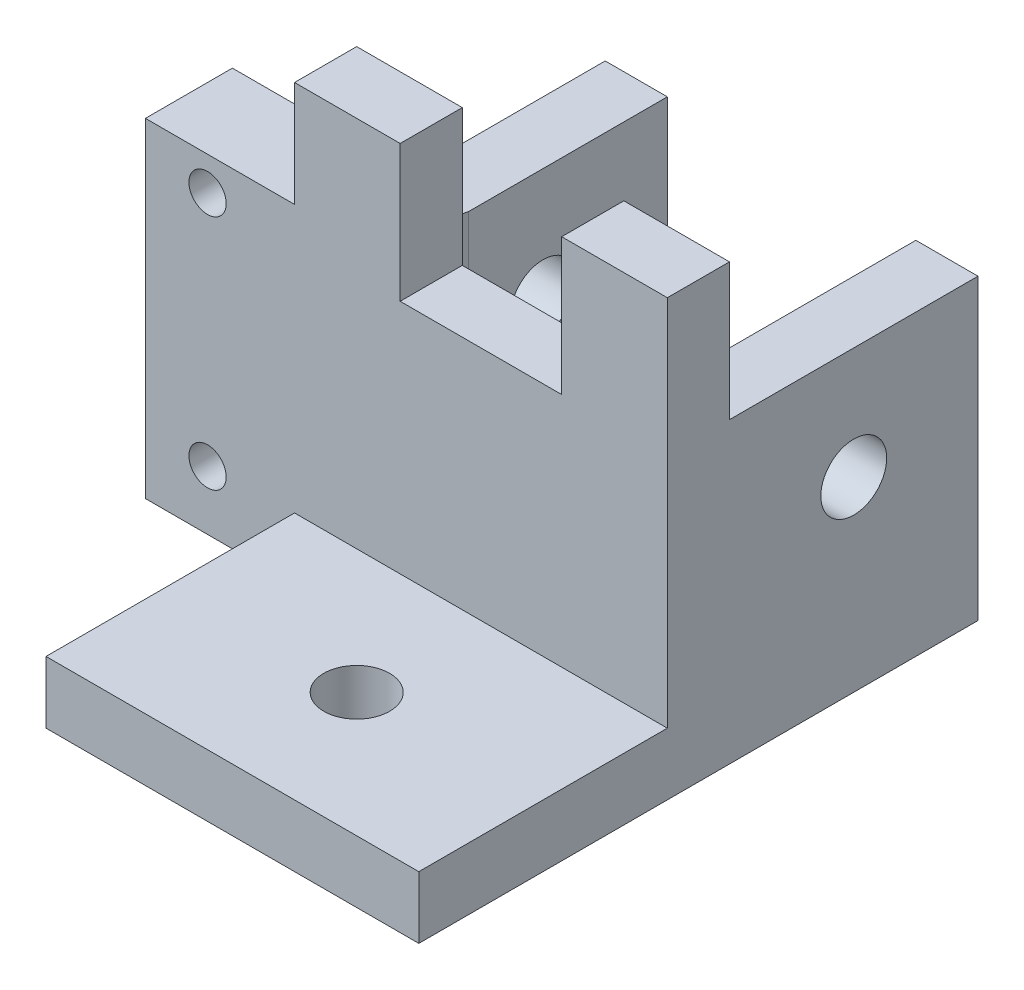
SolidWorks part; units mm, degrees
ref_plane "Front Plane" through (0, 0, 0) normal (0, 0, 1) x (1, 0, 0)
ref_plane "Top Plane" through (0, 0, 0) normal (0, 1, 0) x (1, 0, 0)
ref_plane "Right Plane" through (0, 0, 0) normal (1, 0, 0) x (0, 0, -1)
sketch "Sketch1" plane through (0, 0, 0) normal (0, 1, 0) x (1, 0, 0)
  line L1 (0, 0) -> (30, 0)
  line L2 (0, 0) -> (0, 45)
  line L3 (0, 45) -> (30, 45)
  line L4 (30, 0) -> (30, 45)
  dimension "D1" = 30
  dimension "D2" = 45
extrude "Boss-Extrude1" add sketch "Sketch1" along normal blind 5
sketch "Sketch2" plane through (0, 5, 0) normal (0, 1, 0) x (1, 0, 0)
  line L11 (0, 45) -> (0, 0) construction
  line L12 (0, 25) -> (30, 25)
  line L13 (0, 25) -> (0, 20)
  line L14 (0, 20) -> (30, 20)
  line L15 (30, 25) -> (30, 20)
  line L16 (30, 0) -> (30, 45) construction
  line L17 (30, 45) -> (0, 45) construction
  dimension "D1" = 5
  dimension "D2" = 20
extrude "Boss-Extrude2" add sketch "Sketch2" along normal blind 30
sketch "Sketch3" plane through (0, 5, 0) normal (0, 1, 0) x (1, 0, 0)
  line L1 (0, 25) -> (5, 25)
  line L2 (0, 25) -> (0, 45)
  line L3 (0, 45) -> (5, 45)
  line L4 (5, 25) -> (5, 45)
  line L5 (30, 45) -> (0, 45) construction
  line L6 (0, 45) -> (0, 25) construction
  line L7 (25, 45) -> (30, 45)
  line L8 (25, 45) -> (25, 25)
  line L9 (25, 25) -> (30, 25)
  line L10 (30, 45) -> (30, 25)
  line L11 (0, 25) -> (30, 25) construction
  dimension "D1" = 5
  dimension "D2" = 5
  dimension "D3" = 20
  dimension "D4" = 0
extrude "Boss-Extrude3" add sketch "Sketch3" along normal blind 19
sketch "Sketch4" plane through (0, 35, 0) normal (0, 1, 0) x (1, 0, 0)
  line L0 (0, 20) -> (30, 20) construction
  line L1 (8.5, 20) -> (21.5, 20)
  line L2 (8.5, 20) -> (8.5, 25)
  line L3 (8.5, 25) -> (21.5, 25)
  line L4 (21.5, 20) -> (21.5, 25)
  line L5 (0, 25) -> (30, 25) construction
  line L6 (0, 25) -> (0, 20) construction
  dimension "D1" = 13
  dimension "D2" = 8.5
extrude "Cut-Extrude1" cut sketch "Sketch4" against normal blind 11
sketch "Sketch5" plane through (0, 0, 0) normal (0, -1, 0) x (1, 0, 0)
  line L0 (0, 0) -> (30, 0) construction
  line L1 (30, 0) -> (30, -45) construction
  line L2 (30, -45) -> (0, -45) construction
  circle A0 centre (15, -10) radius 2.65
  circle A1 centre (15, -35) radius 2.65
  dimension "D1" = 5.3
  dimension "D4" = 5.3
  dimension "D2" = 10
  dimension "D3" = 15
  dimension "D5" = 10
  dimension "D6" = 15
extrude "Cut-Extrude2" cut sketch "Sketch5" against normal blind 10
sketch "Sketch6" plane through (30, 0, 0) normal (1, 0, 0) x (0, 0, -1)
  line L0 (45, 24) -> (45, 0) construction
  line L1 (0, 0) -> (45, 0) construction
  circle A0 centre (35, 15) radius 2.65
  dimension "D1" = 5.3
  dimension "D2" = 10
  dimension "D3" = 15
extrude "Cut-Extrude3" cut sketch "Sketch6" against normal through all both and the other way through all
sketch "Sketch7" plane through (0, 0, -45) normal (0, 0, -1) x (-1, 0, 0)
  line L0 (-25, 5) -> (-26, 5)
  line L1 (-26, 5) -> (-25, 9)
  line L2 (-25, 24) -> (-25, 5) construction
  line L3 (-25, 9) -> (-25, 5)
  line L4 (-5, 5) -> (-4, 5)
  line L5 (-4, 5) -> (-5, 9)
  line L6 (-5, 24) -> (-5, 5) construction
  line L7 (-5, 9) -> (-5, 5)
  dimension "D1" = 4
  dimension "D2" = 4
  dimension "D3" = 1
  dimension "D4" = 1
extrude "Cut-Extrude4" cut sketch "Sketch7" against normal up to surface (20 mm away) up to face at (15, 24.5, -25)
sketch "Sketch8" plane through (0, 24, 0) normal (0, 1, 0) x (1, 0, 0)
  line L0 (25, 25) -> (26, 25)
  line L1 (25, 25) -> (30, 25) construction
  line L2 (26, 25) -> (25, 29)
  line L3 (25, 45) -> (25, 25) construction
  line L4 (25, 29) -> (25, 25)
  line L5 (5, 25) -> (5, 29)
  line L6 (5, 25) -> (5, 45) construction
  line L7 (5, 29) -> (4, 25)
  line L8 (8.5, 25) -> (0, 25) construction
  line L9 (4, 25) -> (5, 25)
  dimension "D1" = 1
  dimension "D2" = 4
  dimension "D3" = 1
  dimension "D4" = 4
extrude "Cut-Extrude5" cut sketch "Sketch8" against normal up to surface (19 mm away) up to face at (15, 5, -12.65)
sketch "Sketch9" plane through (0, 0, 0) normal (-1, 0, 0) x (0, 0, 1)
  line L0 (-45, 0) -> (0, 0) construction
  line L1 (-25, 26.5) -> (-20, 26.5)
  line L2 (-25, 26.5) -> (-25, 0)
  line L3 (-25, 0) -> (-20, 0)
  line L4 (-20, 26.5) -> (-20, 0)
  line L5 (-20, 35) -> (-20, 5) construction
  line L7 (-25, 35) -> (-25, 24) construction
  dimension "D1" = 26.5
extrude "Boss-Extrude4" add sketch "Sketch9" along normal blind 12
sketch "Sketch10" plane through (0, 0, -25) normal (0, 0, -1) x (-1, 0, 0)
  line L0 (12, 26.5) -> (12, 0) construction
  line L1 (12, 0) -> (0, 0)
  line L2 (12, 0) -> (12, 9)
  line L3 (12, 9) -> (0, 9)
  line L4 (0, 0) -> (0, 9)
  line L5 (12, 0) -> (0, 0) construction
  line L6 (0, 24) -> (0, 0) construction
  line L7 (12, 26.5) -> (0, 26.5)
  line L8 (12, 26.5) -> (12, 19.5)
  line L9 (12, 19.5) -> (0, 19.5)
  line L10 (0, 26.5) -> (0, 19.5)
  line L11 (12, 26.5) -> (0, 26.5) construction
  dimension "D1" = 9
  dimension "D2" = 7
extrude "Boss-Extrude5" add sketch "Sketch10" along normal blind 2
chamfer "Chamfer1" distance 2 angle 45 1 edges at (-6, 19.5, -27)
chamfer "Chamfer2" distance 2 angle 45 1 edges at (-6, 9, -27)
sketch "Sketch11" plane through (0, 0, -27) normal (0, 0, -1) x (-1, 0, 0)
  line L0 (12, 26.5) -> (0, 26.5) construction
  line L1 (12, 21.5) -> (12, 26.5) construction
  circle A0 centre (7, 23.8) radius 1.5
  circle A1 centre (7, 4.75) radius 1.5
  dimension "D1" = 3
  dimension "D2" = 3
  dimension "D3" = 19.05
  dimension "D4" = 2.7
  dimension "D5" = 5
extrude "Cut-Extrude6" cut sketch "Sketch11" against normal through all
